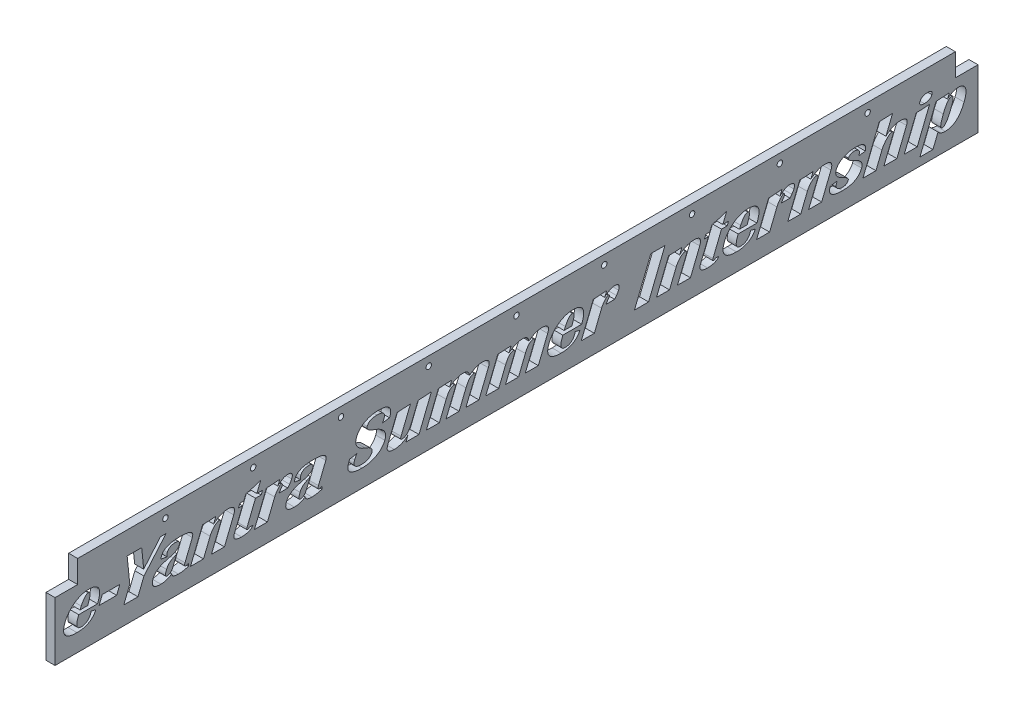
SolidWorks part; units mm, degrees
material "Acrylic (Medium-high impact)"
ref_plane "Front Plane" through (0, 0, 0) normal (0, 0, 1) x (1, 0, 0)
ref_plane "Top Plane" through (0, 0, 0) normal (0, 1, 0) x (1, 0, 0)
ref_plane "Right Plane" through (0, 0, 0) normal (1, 0, 0) x (0, 0, -1)
sketch "Sketch1" plane through (0, 0, 0) normal (0, 0, 1) x (1, 0, 0)
  line L6 (25, 5) -> (25, 95)
  line L7 (25, 95) -> (15, 95)
  line L8 (15, 95) -> (15, 5)
  line L12 (15, 5) -> (25, 5)
  dimension "D1" = 10
extrude "Boss-Extrude1" add sketch "Sketch1" along normal blind 1020
sketch "Sketch2" plane through (25, 0, 0) normal (1, 0, 0) x (0, 0, -1)
  line L0 (-1052.1126, 85) -> (45.5589, 85) construction
  line L1 (-1020, 95) -> (-995, 95)
  line L2 (-1020, 95) -> (-1020, 70)
  line L3 (-1020, 70) -> (-995, 70)
  line L4 (-995, 95) -> (-995, 70)
  line L5 (0, 95) -> (-25, 95)
  line L6 (0, 95) -> (0, 70)
  line L7 (0, 70) -> (-25, 70)
  line L8 (-25, 95) -> (-25, 70)
  line L9 (-1020, 95) -> (0, 95) construction
  dimension "D1" = 25
  dimension "D2" = 25
  dimension "D3" = 25
  dimension "D4" = 25
  dimension "D5" = 10
extrude "Cut-Extrude1" cut sketch "Sketch2" against normal blind 10
sketch "Sketch3" plane through (25, 0, 0) normal (1, 0, 0) x (0, 0, -1)
  line L0 (-995, 70) -> (-995, 95) construction
  line L1 (-995, 95) -> (-25, 95) construction
  circle A0 centre (-898, 85) radius 3
  dimension "D3" = 6
  dimension "D1" = 97
  dimension "D2" = 10
extrude "Cut-Extrude2" cut sketch "Sketch3" against normal blind 10
pattern_linear "LPattern1" count 9 spacing 97 along (0, 0, -1) of "Cut-Extrude2"
sketch "Sketch4" plane through (25, 0, 0) normal (1, 0, 0) x (0, 0, -1)
  text T0 "e-Yantra Summer Internship    Programme 2018 " font "Britannic Bold" height 45
extrude "Cut-Extrude3" cut sketch "Sketch4" against normal blind 10
